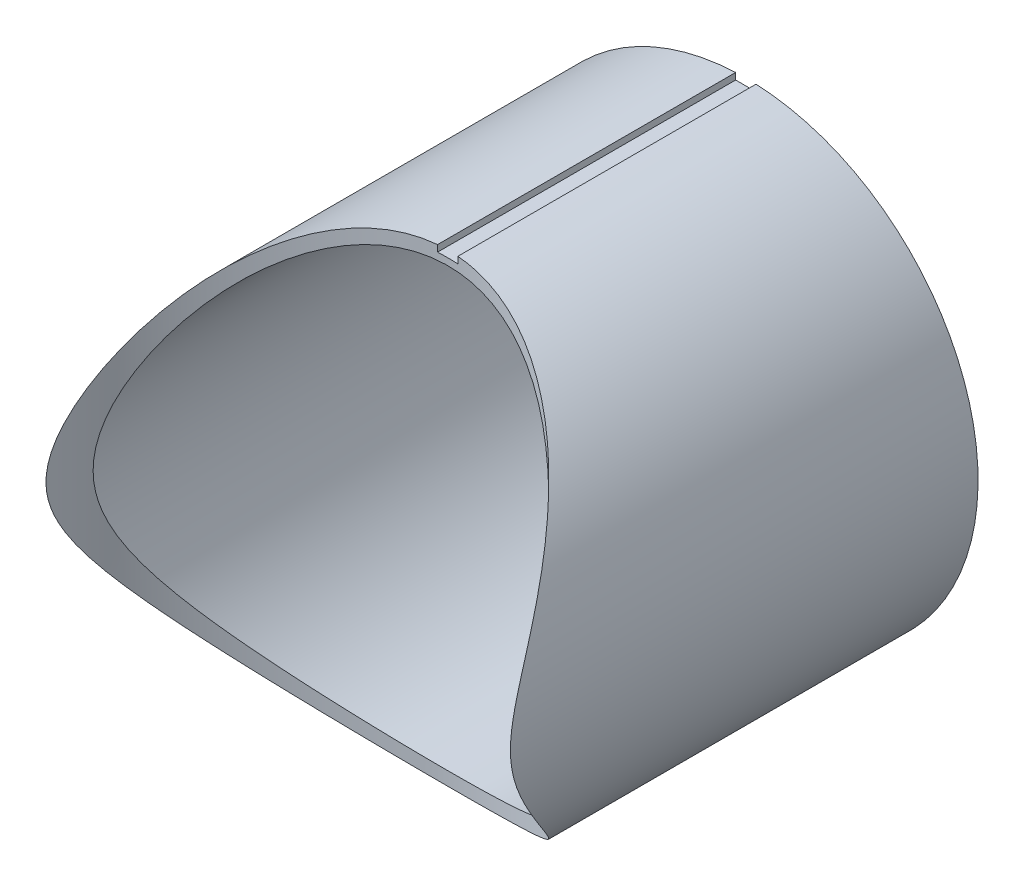
SolidWorks part; units mm, degrees
ref_plane "Front Plane" through (0, 0, 0) normal (0, 0, 1) x (1, 0, 0)
ref_plane "Top Plane" through (0, 0, 0) normal (0, 1, 0) x (1, 0, 0)
ref_plane "Right Plane" through (0, 0, 0) normal (1, 0, 0) x (0, 0, -1)
sketch "Sketch1" plane through (0, 0, 0) normal (0, 0, 1) x (1, 0, 0)
  circle A0 centre (0, 200) radius 15.85 construction
  circle A1 centre (0, 200) radius 15.85 construction
  circle A2 centre (0, 200) radius 16.15
  circle A3 centre (0, 200) radius 17.15
  dimension "D1" = 0.3
  dimension "D2" = 1.3
extrude "Boss-Extrude1" add sketch "Sketch1" against normal blind 40
sketch "Sketch2" plane through (0, 550, 0) normal (0, 1, 0) x (1, 0, 0)
  circle A0 centre (0, 0) radius 18 construction
  circle A1 centre (0, 0) radius 18
extrude "Cut-Extrude1" cut sketch "Sketch2" against normal through all
sketch "Sketch3" plane through (0, 0, -40) normal (0, 0, -1) x (-1, 0, 0)
  line L0 (0, 216.15) -> (0, 217.15) construction
  line L2 (-0.75, 216.65) -> (0.75, 216.65)
  line L3 (-0.75, 216.65) -> (-0.75, 217.1336)
  line L4 (0.75, 216.65) -> (0.75, 217.1336)
  circle A1 centre (0, 200) radius 17.15 construction
  circle A2 centre (0, 200) radius 16.15 construction
  point P12 (0, 216.65)
  dimension "D1" = 1.5
extrude "Cut-Extrude2" cut sketch "Sketch3" against normal through all and the other way through all
